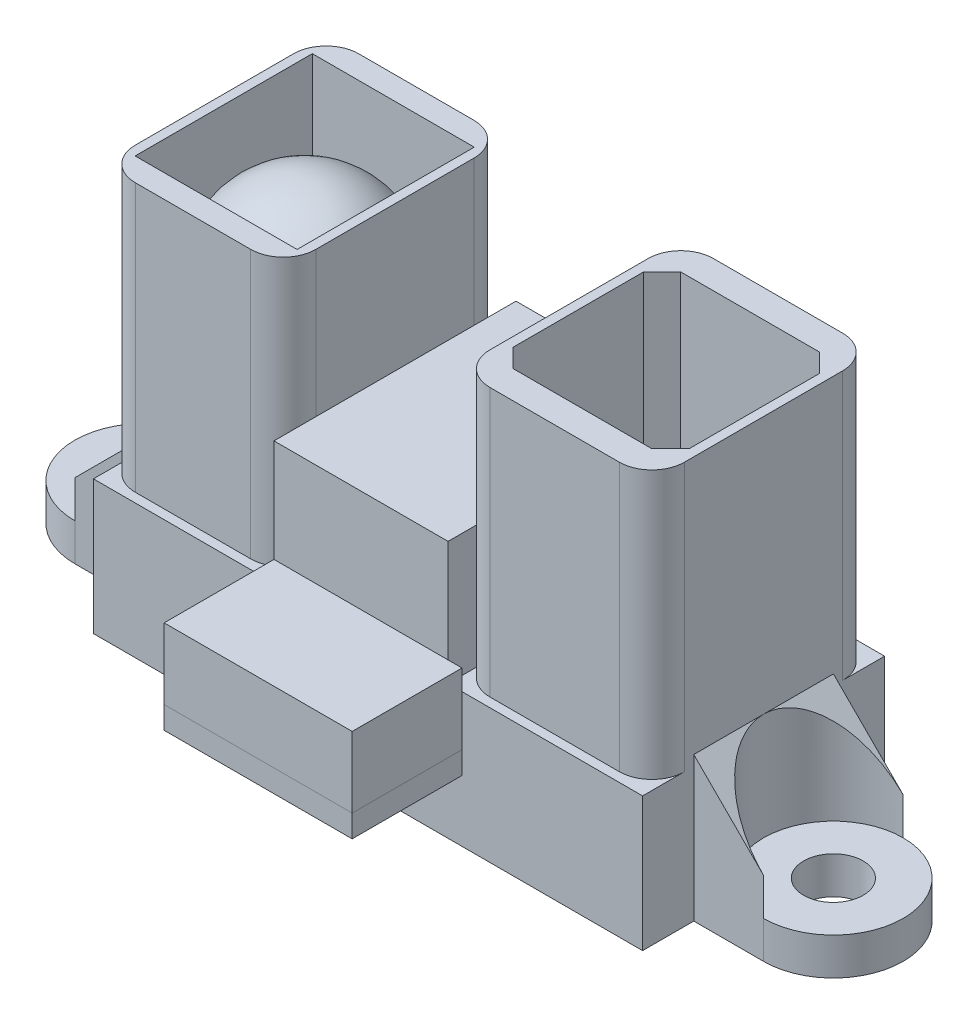
SolidWorks part; units mm, degrees
ref_plane "前视基准面" through (0, 0, 0) normal (0, 0, 1) x (1, 0, 0)
ref_plane "上视基准面" through (0, 0, 0) normal (0, 1, 0) x (1, 0, 0)
ref_plane "右视基准面" through (0, 0, 0) normal (1, 0, 0) x (0, 0, -1)
sketch "草图1" plane through (0, 0, 0) normal (0, 1, 0) x (1, 0, 0)
  line L0 (-18.5, 0) -> (18.5, 0) construction
  line L5 (-14.75, 6.5) -> (14.75, 6.5)
  line L6 (-14.75, 6.5) -> (-14.75, -6.5)
  line L7 (-14.75, -6.5) -> (14.75, -6.5)
  line L8 (14.75, 6.5) -> (14.75, -6.5)
  line L9 (-14.75, 6.5) -> (14.75, -6.5) construction
  line L10 (-14.75, -6.5) -> (14.75, 6.5) construction
  line L11 (-18.5, 3.75) -> (18.5, 3.75)
  line L12 (-18.5, -3.75) -> (18.5, -3.75)
  arc A0 (-18.5, 3.75) -> (-18.5, -3.75) centre (-18.5, 0) ccw
  arc A1 (18.5, -3.75) -> (18.5, 3.75) centre (18.5, 0) ccw
  circle A2 centre (18.5, 0) radius 1.6
  circle A3 centre (-18.5, 0) radius 1.6
  point P0 (0, 0)
  point P9 (0, 0)
  dimension "D2" = 3.75
  dimension "D3" = 3.2
  dimension "D4" = 37
  dimension "D1" = 29.5
  dimension "D5" = 13
extrude "凸台-拉伸1" add sketch "草图1" along normal blind 21.6 contours L12 L6 L7 L8 | L12 A1 L11 L8 A2 | L6 L12 L8 L11 | L6 L11 L8 L5 | L11 A0 L12 L6 A3 region at (0, 0, -5.125) region at (0, 0, 0) region at (-14.8561, 0, 0) region at (16.625, 0, -3.6439) region at (0, 0, 5.125)
sketch "草图2" plane through (0, 0, 6.5) normal (0, 0, 1) x (1, 0, 0)
  line L0 (-18.5, 2) -> (-18.5, 4)
  line L1 (-30, 0) -> (30, 0)
  line L2 (-30, 0) -> (-30, 2)
  line L3 (-30, 2) -> (30, 2)
  line L4 (30, 0) -> (30, 2)
  line L5 (-18.5, 4) -> (-14.75, 7.75)
  line L6 (0, 0) -> (0, 24.1782) construction
  line L7 (18.5, 2) -> (18.5, 4)
  line L8 (-14.75, 0) -> (14.75, 0)
  line L9 (14.75, 0) -> (14.75, 21.6)
  line L10 (14.75, 21.6) -> (-14.75, 21.6)
  line L11 (-14.75, 21.6) -> (-14.75, 0)
  line L12 (-14.75, 0) -> (14.75, 0)
  line L13 (14.75, 0) -> (14.75, 21.6)
  line L14 (14.75, 21.6) -> (-14.75, 21.6)
  line L15 (-14.75, 21.6) -> (-14.75, 0)
  line L16 (18.5, 4) -> (14.75, 7.75)
  line L17 (-18.5, 21.6) -> (-18.5, 0) construction
  line L18 (22.25, 0) -> (22.25, 21.6) construction
  line L19 (-22.25, 21.6) -> (22.25, 21.6)
  line L20 (-22.25, 21.6) -> (-22.25, 0)
  line L21 (-22.25, 0) -> (22.25, 0)
  line L22 (22.25, 21.6) -> (22.25, 0)
  line L24 (-5.05, 13.8157) -> (5.05, 13.8157)
  line L25 (-5.05, 13.8157) -> (-5.05, 21.6)
  line L26 (-5.05, 21.6) -> (5.05, 21.6)
  line L27 (5.05, 13.8157) -> (5.05, 21.6)
  line L28 (-5.05, 13.8157) -> (5.05, 21.6) construction
  line L29 (-5.05, 21.6) -> (5.05, 13.8157) construction
  point P26 (0, 17.7079)
  line M15 (-14.75, 21.6) -> (-14.75, 0)
  dimension "D1" = 2
  dimension "D3" = 45
  dimension "D4" = 2
  dimension "D5" = 60
  dimension "D6" = 10.1
  dimension "D2" = 0
extrude "切除-拉伸1" cut sketch "草图2" against normal blind 21.6 contours L19 L20 L3 L0 L5 M15 | L22 L19 L13 L16 L7 L3 | L24 L27 L19 L25 region at (-18.7389, 12.6459, 6.5) region at (18.7389, 12.6459, 6.5) region at (0, 17.7079, 6.5)
sketch "草图13" plane through (0, 2, 0) normal (0, 1, 0) x (1, 0, 0)
  circle A0 centre (-18.5, 0) radius 3.75
  circle A1 centre (18.5, 0) radius 3.75
extrude "切除-拉伸7" cut sketch "草图13" along normal through all
ref_plane "基准面1" through (0, 7.2, 0) normal (0, 1, 0) x (1, 0, 0)
sketch "草图4" plane through (0, 7.2, 0) normal (0, 1, 0) x (1, 0, 0)
  line L1 (-14.75, 6.5) -> (-5.05, 6.5)
  line L2 (-14.75, 4.25) -> (-14.75, -4.25)
  line L3 (-14.75, -6.5) -> (-5.05, -6.5)
  line L4 (-5.05, 4.25) -> (-5.05, -4.25)
  line L5 (-14.75, 6.5) -> (-5.05, -6.5) construction
  line L6 (-14.75, -6.5) -> (-5.05, 6.5) construction
  line L7 (-13, 6) -> (-6.8, 6)
  line L8 (-14.75, 6.5) -> (-14.75, -6.5)
  line L9 (-13, -6) -> (-6.8, -6)
  line L10 (-5.05, 6.5) -> (-5.05, -6.5)
  line L11 (-14.75, 6.5) -> (-5.05, -6.5) construction
  line L12 (-14.75, -6.5) -> (-5.05, 6.5) construction
  arc A0 (-5.05, -4.25) -> (-6.8, -6) centre (-6.8, -4.25) cw
  arc A1 (-14.75, -4.25) -> (-13, -6) centre (-13, -4.25) ccw
  arc A2 (-6.8, 6) -> (-5.05, 4.25) centre (-6.8, 4.25) cw
  arc A3 (-14.75, 4.25) -> (-13, 6) centre (-13, 4.25) cw
  point P0 (-9.9, 0)
  point P6 (-9.9, 0)
  dimension "D2" = 1.75
  dimension "D1" = 0.5
extrude "切除-拉伸2" cut sketch "草图4" along normal through all contours A1 L8 L3 L10 A0 L9 | L8 A3 L7 A2 L10 L1 region at (-9.9, 7.2, -6.1133) region at (-9.9, 7.2, 6.1133)
sketch "草图6" plane through (0, 21.6, 0) normal (0, 1, 0) x (1, 0, 0)
  line L0 (-5.05, -6.5) -> (5.05, -6.5) construction
  line L1 (14.75, 6.5) -> (4.3, 6.5)
  line L2 (14.75, 6.5) -> (14.75, -6.5)
  line L3 (14.75, -6.5) -> (4.3, -6.5)
  line L4 (4.3, 6.5) -> (4.3, -6.5)
  dimension "D1" = 10.45
extrude "凸台-拉伸2" add sketch "草图6" against normal up to surface (7.7843 mm away) up to face at (-1.6833, 13.8157, 0)
sketch "草图5" plane through (0, 21.6, 0) normal (0, 1, 0) x (1, 0, 0)
  line L0 (14.75, 0) -> (4.3, 0) construction
  line L1 (14.75, 6.5) -> (4.3, 6.5)
  line L2 (14.75, 6.5) -> (14.75, -6.5)
  line L3 (14.75, -6.5) -> (4.3, -6.5)
  line L4 (4.3, 6.5) -> (4.3, -6.5)
  line L5 (6.05, 6) -> (13, 6)
  line L6 (4.3, 4.25) -> (4.3, -4.25)
  line L7 (6.05, -6) -> (13, -6)
  line L8 (14.75, 4.25) -> (14.75, -4.25)
  arc A0 (4.3, -4.25) -> (6.05, -6) centre (6.05, -4.25) ccw
  arc A1 (13, -6) -> (14.75, -4.25) centre (13, -4.25) ccw
  arc A2 (13, 6) -> (14.75, 4.25) centre (13, 4.25) cw
  arc A3 (6.05, 6) -> (4.3, 4.25) centre (6.05, 4.25) ccw
  point P16 (14.75, -6)
  point P21 (4.3, 6)
  line M14 (14.75, -6.5) -> (14.75, 6.5)
  line M15 (14.75, 6.5) -> (4.3, 6.5)
  line M17 (4.3, -6.5) -> (14.75, -6.5)
  line M18 (4.3, 6.5) -> (4.3, -6.5)
  dimension "D3" = 1.75
  dimension "D1" = 10.45
  dimension "D2" = 0.5
extrude "切除-拉伸3" cut sketch "草图5" against normal up to surface (14.4 mm away) contours A1 L7 A0 M18 M17 M14 | A3 L5 A2 M14 M15 M18 region at (9.525, 21.6, -6.1212) region at (9.525, 21.6, 6.1212) up to face at (-9.9, 7.2, 5.7041)
sketch "草图7" plane through (0, 21.6, 0) normal (0, 1, 0) x (1, 0, 0)
  line L0 (-14.75, 4.25) -> (-5.05, -4.25) construction
  line L1 (-14.25, 4.7585) -> (-5.55, 4.7585)
  line L2 (-14.25, 4.7585) -> (-14.25, -4.7585)
  line L3 (-14.25, -4.7585) -> (-5.55, -4.7585)
  line L4 (-5.55, 4.7585) -> (-5.55, -4.7585)
  line L5 (-14.25, 4.7585) -> (-5.55, -4.7585) construction
  line L6 (-14.25, -4.7585) -> (-5.55, 4.7585) construction
  line L7 (-14.75, -4.25) -> (-5.05, 4.25) construction
  line L9 (-14.75, 4.25) -> (-14.75, -4.25) construction
  circle A0 centre (-9.9, 0) radius 4.7585
  point P0 (-9.9, 0)
  point P14 (-9.9, 0)
  dimension "D2" = 4.85
  dimension "D1" = 0.5
extrude "切除-拉伸4" cut sketch "草图7" against normal blind 6 contours L4 A0 L2 region at (-9.9, 21.6, 0)
sketch "草图8" plane through (0, 21.6, 0) normal (0, 1, 0) x (1, 0, 0)
  line L1 (-14.25, 4.7585) -> (-5.55, 4.7585)
  line L2 (-14.25, 4.7585) -> (-14.25, -4.7585)
  line L3 (-14.25, -4.7585) -> (-5.55, -4.7585)
  line L4 (-5.55, 4.7585) -> (-5.55, -4.7585)
extrude "切除-拉伸5" cut sketch "草图8" against normal blind 5
ref_axis "发射方向" through (-9.9, 15.6, 0) along (0, 1, 0)
ref_plane "基准面2" through (-9.9, 0, 0) normal (1, 0, 0) x (0, 1, 0)
sketch "草图9" plane through (-9.9, 0, 0) normal (1, 0, 0) x (0, 1, 0)
  line L0 (15.6, -1.929) -> (15.6, 1.929) construction
  line L1 (15.6, -1.929) -> (15.6, 1.929) construction
  line L2 (15.6, 1.929) -> (15.6, 4.7585) construction
  line L3 (15.6, 1.929) -> (15.6, 4.7585) construction
  line L4 (15.6, 0) -> (15.6, 4.7585)
  line L5 (15.6, 0) -> (20.3585, 0)
  arc A0 (20.3585, 0) -> (15.6, 4.7585) centre (15.6, 0) ccw
revolve "旋转1" add sketch "草图9" angle 360 about L5
sketch "草图10" plane through (0, 21.6, 0) normal (0, 1, 0) x (1, 0, 0)
  line L0 (14.75, 0) -> (4.3, 0) construction
  line L1 (14.75, 4.25) -> (14.75, -4.25) construction
  line L2 (4.3, 4.25) -> (4.3, -4.25) construction
  line L3 (9.525, -6) -> (9.525, 6) construction
  line L4 (6.05, -6) -> (13, -6) construction
  line L5 (13, 6) -> (6.05, 6) construction
  line L6 (6.05, 6) -> (13, 6) construction
  line L7 (5.8, 4.5) -> (13.25, 4.5)
  line L8 (4.8, 3.5) -> (4.8, -3.5)
  line L9 (5.8, -4.5) -> (13.25, -4.5)
  line L10 (14.25, 3.5) -> (14.25, -3.5)
  line L11 (4.8, 4.5) -> (14.25, -4.5) construction
  line L12 (4.8, -4.5) -> (14.25, 4.5) construction
  line L13 (5.8, 4.5) -> (4.8, 3.5)
  line L14 (13.25, 4.5) -> (14.25, 3.5)
  line L15 (4.8, -3.5) -> (5.8, -4.5)
  line L16 (13.25, -4.5) -> (14.25, -3.5)
  point P12 (9.525, 0)
  point P13 (9.525, 0)
  dimension "D1" = 1.5
  dimension "D2" = 0.5
extrude "切除-拉伸6" cut sketch "草图10" against normal blind 15
sketch "草图11" plane through (0, 0, 6.5) normal (0, 0, 1) x (1, 0, 0)
  line L0 (0, 0) -> (0, 7.8) construction
  line L1 (-14.75, 0) -> (14.75, 0) construction
  line L2 (-5.05, 3.3) -> (5.05, 3.3)
  line L3 (-5.05, 3.3) -> (-5.05, 4.5)
  line L4 (-5.05, 4.5) -> (5.05, 4.5)
  line L5 (5.05, 3.3) -> (5.05, 4.5)
  line L6 (-5.05, 3.3) -> (5.05, 4.5) construction
  line L7 (-5.05, 4.5) -> (5.05, 3.3) construction
  point P3 (0, 3.9)
  dimension "D1" = 3.3
  dimension "D2" = 10.1
  dimension "D3" = 1.2
extrude "凸台-拉伸3" add sketch "草图11" along normal blind 5.9
sketch "草图12" plane through (0, 0, 6.5) normal (0, 0, 1) x (1, 0, 0)
  line L1 (-5.05, 4.5) -> (5.05, 4.5)
  line L2 (-5.05, 4.5) -> (-5.05, 8.3)
  line L3 (-5.05, 8.3) -> (5.05, 8.3)
  line L4 (5.05, 4.5) -> (5.05, 8.3)
  dimension "D1" = 3.8
extrude "凸台-拉伸4" add sketch "草图12" along normal blind 5.9 separate body
sketch "草图14" plane through (0, 6.6, 0) normal (0, 1, 0) x (1, 0, 0)
  point P0 (9.525, 0)
ref_axis "接收方向" through (9.525, 6.6, 0) along (0, 1, 0)
